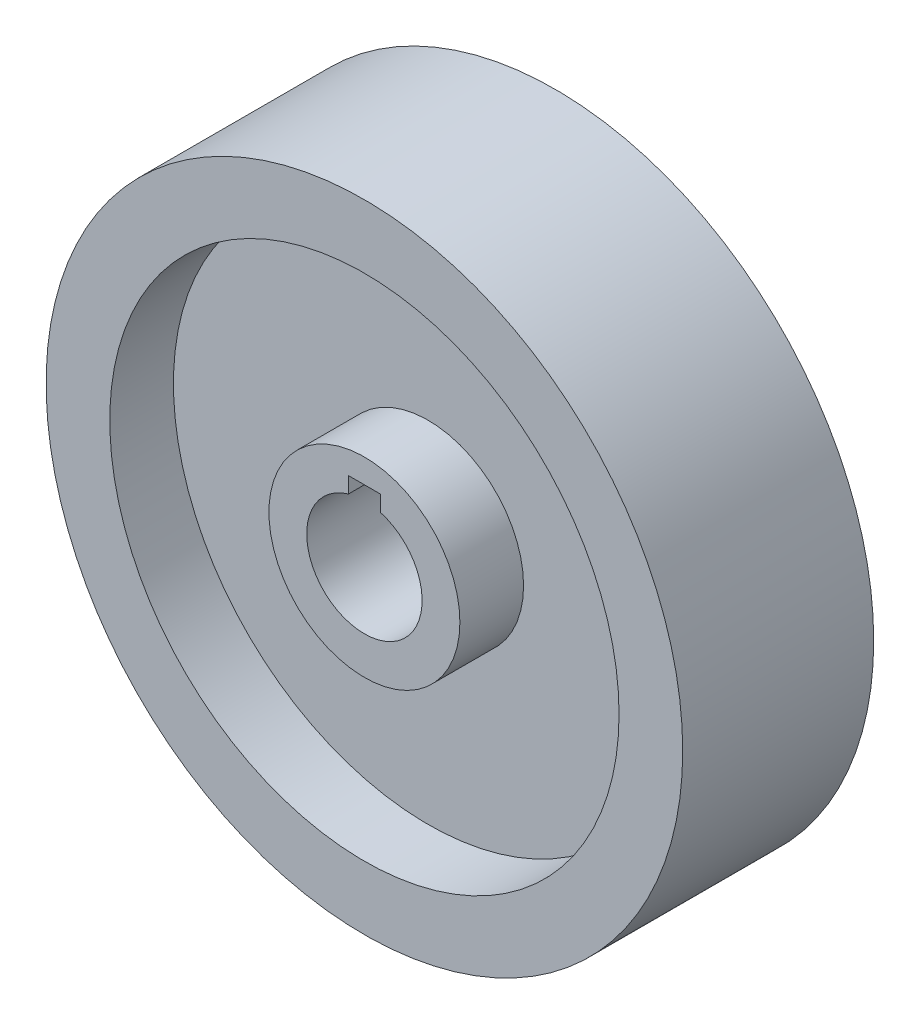
SolidWorks part; units mm, degrees
ref_plane "Front Plane" through (0, 0, 0) normal (0, 0, 1) x (1, 0, 0)
ref_plane "Top Plane" through (0, 0, 0) normal (0, 1, 0) x (1, 0, 0)
ref_plane "Right Plane" through (0, 0, 0) normal (1, 0, 0) x (0, 0, -1)
sketch "Sketch1" plane through (0, 0, 0) normal (1, 0, 0) x (0, 0, -1)
  line L0 (-34.2145, 0) -> (34.2145, 0) construction
  line L1 (0, 0) -> (0, 63.5) construction
  line L2 (19.05, 11.5094) -> (-19.05, 11.5094)
  line L3 (-19.05, 11.5094) -> (-19.05, 19.05)
  line L4 (-19.05, 19.05) -> (-6.35, 19.05)
  line L5 (-6.35, 19.05) -> (-6.35, 50.8)
  line L6 (-6.35, 50.8) -> (-19.05, 50.8)
  line L7 (-19.05, 50.8) -> (-19.05, 63.5)
  line L8 (-19.05, 63.5) -> (19.05, 63.5)
  line L9 (19.05, 11.5094) -> (19.05, 19.05)
  line L10 (19.05, 19.05) -> (6.35, 19.05)
  line L11 (6.35, 19.05) -> (6.35, 50.8)
  line L12 (6.35, 50.8) -> (19.05, 50.8)
  line L13 (19.05, 50.8) -> (19.05, 63.5)
  point P13 (0, 11.5094)
  dimension "D1" = 38.1
  dimension "D2" = 127
  dimension "D3" = 23.0188
  dimension "D4" = 12.7
  dimension "D5" = 38.1
  dimension "D6" = 12.7
revolve "Revolve1" add sketch "Sketch1" angle 360 about L0
sketch "Sketch4" plane through (0, 0, -19.05) normal (0, 0, -1) x (-1, 0, 0)
  line L0 (-3.175, 11.0628) -> (3.175, 11.0628)
  line L1 (3.175, 11.0628) -> (3.175, 14.2378)
  line L2 (3.175, 14.2378) -> (-3.175, 14.2378)
  line L3 (-3.175, 14.2378) -> (-3.175, 11.0628)
  circle A0 centre (0, 0) radius 11.5094 construction
  dimension "D1" = 6.35
  dimension "D2" = 3.175
extrude "Cut-Extrude1" cut sketch "Sketch4" against normal through all
